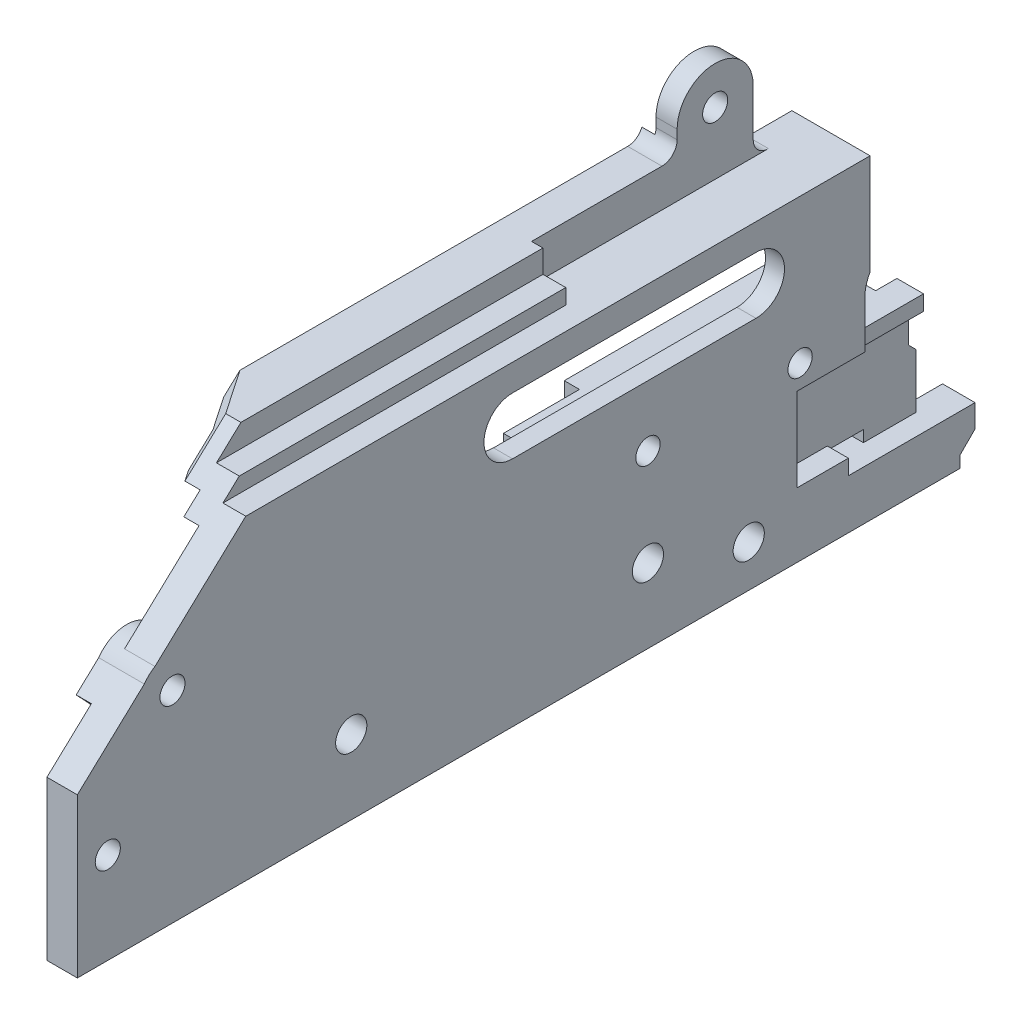
SolidWorks part; units mm, degrees
ref_plane "前视基准面" through (0, 0, 0) normal (0, 0, 1) x (1, 0, 0)
ref_plane "上视基准面" through (0, 0, 0) normal (0, 1, 0) x (1, 0, 0)
ref_plane "右视基准面" through (0, 0, 0) normal (1, 0, 0) x (0, 0, -1)
other "Configuration Table"
sketch "草图1" plane through (0, 0, 0) normal (1, 0, 0) x (0, 0, -1)
  line L0 (0, 0) -> (20, 0) construction
  line L2 (29.2, 6.5) -> (-4, 6.5)
  line L3 (29.2, 6.5) -> (29.2, -15.5)
  line L4 (29.2, -15.5) -> (-4, -15.5)
  line L5 (-4, 6.5) -> (-4, -15.5)
  circle A0 centre (0, 0) radius 1.6
  circle A1 centre (20, 0) radius 1.6
  dimension "D1" = 20
  dimension "D2" = 3.2
  dimension "D4" = 9.2
  dimension "D6" = 4
  dimension "D3" = 6.5
  dimension "D5" = 22
extrude "凸台-拉伸1" add sketch "草图1" along normal blind 7
sketch "草图2" plane through (7, 0, 0) normal (1, 0, 0) x (0, 0, -1)
  line L1 (-4, 6.5) -> (29.2, 6.5)
  line L2 (-4, 6.5) -> (-4, 17)
  line L3 (-4, 17) -> (29.2, 17)
  line L4 (29.2, 6.5) -> (29.2, 17)
  dimension "D1" = 10.5
extrude "凸台-拉伸2" add sketch "草图2" against normal offset from surface (2 mm away) 5 up to face at (0, 0, -1.6)
sketch "草图3" plane through (0, 0, 4) normal (0, 0, 1) x (1, 0, 0)
  line L1 (7, -15.5) -> (1, -15.5)
  line L2 (7, -15.5) -> (7, 6.5)
  line L3 (7, 6.5) -> (3, 6.5)
  line L4 (1, -15.5) -> (1, 4.5)
  line L5 (3, 6.5) -> (3, 4.5)
  line L6 (3, 4.5) -> (1, 4.5)
  line L7 (5, 6.5) -> (0, 6.5) construction
  dimension "D1" = 6
  dimension "D2" = 2
  dimension "D3" = 2
extrude "凸台-拉伸3" add sketch "草图3" along normal blind 60
sketch "草图4" plane through (0, 0, 4) normal (0, 0, 1) x (1, 0, 0)
  line L4 (5, 6.5) -> (7, 6.5)
  line L5 (7, 6.5) -> (7, 17)
  line L6 (7, 17) -> (5, 17)
  line L7 (5, 17) -> (5, 6.5)
  line L8 (5, 6.5) -> (7, 6.5)
  line L9 (7, 6.5) -> (7, 17)
  line L10 (7, 17) -> (5, 17)
  line L11 (5, 17) -> (5, 6.5)
  dimension "D1" = 0
extrude "凸台-拉伸4" add sketch "草图4" along normal blind 38.5
sketch "草图5" plane through (0, 0, 42.5) normal (0, 0, 1) x (1, 0, 0)
  line L0 (7, 6.5) -> (7, 17) construction
  line L1 (7, 6.5) -> (3, 6.5)
  line L2 (7, 6.5) -> (7, 17)
  line L3 (7, 17) -> (3, 17)
  line L4 (3, 6.5) -> (3, 17)
  line L5 (7, 17) -> (5, 17) construction
extrude "凸台-拉伸5" add sketch "草图5" along normal blind 2
sketch "草图6" plane through (0, 0, 44.5) normal (0, 0, 1) x (1, 0, 0)
  line L4 (7, 6.5) -> (7, 17)
  line L5 (7, 17) -> (3, 17)
  line L6 (3, 17) -> (3, 6.5)
  line L7 (3, 6.5) -> (7, 6.5)
  line L8 (7, 6.5) -> (7, 17)
  line L9 (7, 17) -> (3, 17)
  line L10 (3, 17) -> (3, 6.5)
  line L11 (3, 6.5) -> (7, 6.5)
  dimension "D1" = 0
extrude "凸台-拉伸6" add sketch "草图6" along normal up to surface (19.5 mm away) up to face at (3.6667, -1.5, 64)
sketch "草图7" plane through (0, 17, 0) normal (0, 1, 0) x (1, 0, 0)
  line L0 (1, -64) -> (1, -4) construction
  line L1 (7, 29.2) -> (1, 29.2)
  line L2 (7, 29.2) -> (7, -64)
  line L3 (7, -64) -> (1, -64)
  line L4 (1, 29.2) -> (1, -64)
  line L5 (7, -64) -> (3, -64) construction
extrude "凸台-拉伸7" add sketch "草图7" along normal blind 2
sketch "草图8" plane through (1, 0, 0) normal (-1, 0, 0) x (0, 0, 1)
  line L1 (-29.2, 19) -> (64, 19)
  line L2 (-29.2, 19) -> (-29.2, 24)
  line L3 (-29.2, 24) -> (64, 24)
  line L4 (64, 19) -> (64, 24)
  dimension "D1" = 5
extrude "凸台-拉伸8" add sketch "草图8" against normal blind 3
sketch "草图10" plane through (1, 0, 0) normal (-1, 0, 0) x (0, 0, 1)
  line L1 (-29.2, 24) -> (64, 24)
  line L2 (-29.2, 24) -> (-29.2, 22)
  line L3 (-29.2, 22) -> (64, 22)
  line L4 (64, 24) -> (64, 22)
  line L5 (64, 24) -> (64, 17) construction
  dimension "D1" = 2
extrude "凸台-拉伸9" add sketch "草图10" along normal blind 5.5
sketch "草图12" plane through (-4.5, 0, 0) normal (-1, 0, 0) x (0, 0, 1)
  line L0 (64, 24) -> (-29.2, 24) construction
  line L1 (-29.2, 22) -> (-11.2, 22)
  line L2 (-29.2, 22) -> (-29.2, 24)
  line L3 (-29.2, 24) -> (-11.2, 24)
  line L4 (-11.2, 22) -> (-11.2, 24)
  dimension "D1" = 18
extrude "切除-拉伸1" cut sketch "草图12" against normal up to surface (5.5 mm away) up to face at (1, 19.5, 17.4)
sketch "草图13" plane through (1, 0, 0) normal (-1, 0, 0) x (0, 0, 1)
  line L0 (-11.2, 22) -> (64, 22) construction
  line L1 (10.8, 22) -> (-29.2, 22)
  line L2 (10.8, 22) -> (10.8, 17)
  line L3 (10.8, 17) -> (-29.2, 17)
  line L4 (-29.2, 22) -> (-29.2, 17)
  dimension "D1" = 40
extrude "凸台-拉伸10" add sketch "草图13" along normal blind 3.5
sketch "草图14" plane through (-2.5, 0, 0) normal (-1, 0, 0) x (0, 0, 1)
  line L0 (-29.2, 17) -> (10.8, 17) construction
  line L1 (-11.2, 19.8) -> (-9.2, 19.8)
  line L2 (-11.2, 19.8) -> (-11.2, 17)
  line L3 (-11.2, 17) -> (-9.2, 17)
  line L4 (-9.2, 19.8) -> (-9.2, 17)
  line L5 (10.8, 22) -> (-11.2, 22) construction
  line L6 (-11.2, 22) -> (-11.2, 24) construction
  dimension "D1" = 2
  dimension "D2" = 2.2
sketch "草图15" plane through (4, 0, 0) normal (1, 0, 0) x (0, 0, -1)
  line L0 (29.2, 19) -> (-64, 19) construction
  line L1 (29.2, 24) -> (13.7, 24)
  line L2 (29.2, 24) -> (29.2, 19)
  line L3 (29.2, 19) -> (13.7, 19)
  line L4 (13.7, 24) -> (13.7, 19)
  line L6 (11.2, 22) -> (11.2, 24) construction
  dimension "D1" = 2.5
extrude "切除-拉伸2" cut sketch "草图15" against normal up to next
sketch "草图16" plane through (0, 22, 0) normal (0, 1, 0) x (1, 0, 0)
  line L4 (1, 11.2) -> (1, 13.7)
  line L5 (1, 13.7) -> (-2.5, 13.7)
  line L6 (-2.5, 13.7) -> (-2.5, 11.2)
  line L7 (-2.5, 11.2) -> (1, 11.2)
  line L8 (1, 11.2) -> (1, 13.7)
  line L9 (1, 13.7) -> (-2.5, 13.7)
  line L10 (-2.5, 13.7) -> (-2.5, 11.2)
  line L11 (-2.5, 11.2) -> (1, 11.2)
  dimension "D1" = 0
extrude "凸台-拉伸12" add sketch "草图16" along normal up to surface (2 mm away) up to face at (0.1667, 24, 13.0333)
sketch "草图17" plane through (7, 0, 0) normal (1, 0, 0) x (0, 0, -1)
  line L0 (-47.5, 24) -> (-64, 8.6135)
  line L1 (-64, 24) -> (13.7, 24) construction
  line L2 (-64, -15.5) -> (-64, 19) construction
  line L3 (-64, 8.6135) -> (-64, 24)
  line L4 (-64, 24) -> (-47.5, 24)
  dimension "D1" = 133
  dimension "D2" = 16.5
extrude "切除-拉伸3" cut sketch "草图17" against normal up to next
chamfer "倒角1" distance 3.5 angle 45 1 edges at (-4.5, 23, 48.5724)
sketch "草图18" plane through (-2.5, 0, 0) normal (-1, 0, 0) x (0, 0, 1)
  line L0 (-13.7, 19) -> (-13.7, 24) construction
  line L1 (-29.2, 19) -> (-13.7, 19) construction
  line L2 (-11.337, 27.2) -> (-11.337, 24)
  line L3 (-13.7, 24) -> (-11.2, 24) construction
  line L4 (-11.337, 24) -> (-13.7, 24)
  line L5 (-13.7, 24) -> (-13.7, 19)
  line L6 (-13.7, 19) -> (-21.337, 19)
  line L7 (-21.337, 19) -> (-21.337, 27.2)
  circle A0 centre (-16.337, 27.2) radius 1.65
  arc A1 (-11.337, 27.2) -> (-21.337, 27.2) centre (-16.337, 27.2) ccw
  dimension "D1" = 2.637
  dimension "D2" = 8.2
  dimension "D3" = 3.3
  dimension "D4" = 10
extrude "凸台-拉伸13" add sketch "草图18" against normal blind 2
fillet "圆角1" radius 2 2 edges at (-1.5, 24, -11.337) (-1.5, 19, -21.337)
sketch "草图19" plane through (0, 24, 0) normal (0, 1, 0) x (1, 0, 0)
  line L0 (-0.5, 9.337) -> (-0.5, 11.337) construction
  line L1 (4, 13.7) -> (-0.5, 13.7)
  line L2 (4, 13.7) -> (4, -7.8)
  line L3 (4, -7.8) -> (-0.5, -7.8)
  line L4 (-0.5, 13.7) -> (-0.5, -7.8)
  line L5 (-2.5, -10.8) -> (1, -10.8) construction
  dimension "D1" = 3
extrude "切除-拉伸4" cut sketch "草图19" against normal up to surface (5 mm away) up to face at (2, 19, -3.3438)
chamfer "倒角2" distance 3 angle 45 2 edges at (4, 24, 27.65) (1, 22, 30.2224)
sketch "草图20" plane through (7, 0, 0) normal (1, 0, 0) x (0, 0, -1)
  line L0 (-64, -15.5) -> (-64, 8.6135) construction
  line L1 (-64, -15.5) -> (29.2, -15.5) construction
  circle A0 centre (-62.5, 4) radius 1.65
  dimension "D1" = 1.5
  dimension "D2" = 19.5
  dimension "D3" = 3.3
extrude "切除-拉伸5" cut sketch "草图20" against normal up to next
sketch "草图21" plane through (1, 0, 0) normal (-1, 0, 0) x (0, 0, 1)
  circle A0 centre (62.5, 4) radius 1.65
  circle A1 centre (62.5, 4) radius 4.5
  dimension "D1" = 9
extrude "凸台-拉伸14" add sketch "草图21" against normal up to surface (6 mm away) up to face at (7, 3.3734, 35.3303)
sketch "草图22" plane through (1, 0, 0) normal (-1, 0, 0) x (0, 0, 1)
  line L3 (66.1986, 6.5633) -> (75, -1.6442)
  line L4 (75, -1.6442) -> (75, -15.5)
  line L5 (75, -15.5) -> (64, -15.5)
  line L6 (55.0066, 17) -> (64, 8.6135) construction
  line L7 (64, -0.2426) -> (64, -15.5)
  circle A2 centre (62.5, 4) radius 1.65 construction
  arc A3 (64, -0.2426) -> (58.0279, 4.5) centre (62.5, 4) ccw construction
  arc A4 (64, -0.2426) -> (66.1986, 6.5633) centre (62.5, 4) ccw
  dimension "D1" = 12.5
extrude "凸台-拉伸15" add sketch "草图22" against normal up to surface (6 mm away) up to face at (7, 3.3734, 36.2088)
sketch "草图23" plane through (7, 0, 0) normal (1, 0, 0) x (0, 0, -1)
  line L0 (-64, 8.6135) -> (-64.799, 7.8684)
  line L1 (-64.799, 7.8684) -> (-64, 8.2426)
  line L2 (-64, 8.2426) -> (-64, 8.6135)
  line L3 (-64, 8.6135) -> (-52.8618, 19) construction
  arc A0 (-64, 8.2426) -> (-66.1986, 6.5633) centre (-62.5, 4) ccw construction
extrude "凸台-拉伸16" add sketch "草图23" against normal up to surface (4 mm away) up to face at (3, 9.2872, 41.6414)
sketch "草图24" plane through (1, 0, 0) normal (-1, 0, 0) x (0, 0, 1)
  line L0 (75, -15.5) -> (75, -1.6442) construction
  line L1 (75, -15.5) -> (4, -15.5) construction
  circle A0 centre (71, -10.5) radius 1.65
  dimension "D1" = 3.3
  dimension "D2" = 4
  dimension "D3" = 5
extrude "切除-拉伸6" cut sketch "草图24" against normal up to next
sketch "草图25" plane through (5, 0, 0) normal (-1, 0, 0) x (0, 0, 1)
  line L0 (-29.2, 11.75) -> (42.5, 11.75) construction
  line L1 (-29.2, 6.5) -> (-29.2, 17) construction
  line L2 (42.5, 17) -> (42.5, 6.5) construction
  line L3 (17.8, 11.75) -> (-14.2, 11.75) construction
  line L4 (17.8, 8) -> (-14.2, 8)
  line L5 (17.8, 15.5) -> (-14.2, 15.5)
  arc A0 (17.8, 8) -> (17.8, 15.5) centre (17.8, 11.75) ccw
  arc A1 (-14.2, 15.5) -> (-14.2, 8) centre (-14.2, 11.75) ccw
  point P8 (1.8, 11.75)
  dimension "D1" = 47
  dimension "D2" = 15
  dimension "D3" = 7.5
extrude "切除-拉伸7" cut sketch "草图25" against normal up to next
sketch "草图26" plane through (0, 0, 42.5) normal (0, 0, -1) x (-1, 0, 0)
  line L4 (-5, 17) -> (-5, 6.5)
  line L5 (-5, 6.5) -> (-3, 6.5)
  line L6 (-3, 6.5) -> (-3, 17)
  line L7 (-3, 17) -> (-5, 17)
  line L8 (-5, 17) -> (-5, 6.5)
  line L9 (-5, 6.5) -> (-3, 6.5)
  line L10 (-3, 6.5) -> (-3, 17)
  line L11 (-3, 17) -> (-5, 17)
  dimension "D1" = 0
extrude "切除-拉伸8" cut sketch "草图26" against normal blind 5
sketch "草图27" plane through (0, 0, 4) normal (0, 0, 1) x (1, 0, 0)
  line L1 (1, 4.5) -> (3, 4.5)
  line L2 (1, 4.5) -> (1, 6.5)
  line L3 (1, 6.5) -> (3, 6.5)
  line L4 (3, 4.5) -> (3, 6.5)
extrude "凸台-拉伸17" add sketch "草图27" along normal blind 10
sketch "草图28" plane through (1, 0, 0) normal (-1, 0, 0) x (0, 0, 1)
  line L0 (67, 1.4943) -> (67, -15.5)
  line L2 (75, -15.5) -> (4, -15.5) construction
  line L3 (67, -15.5) -> (75, -15.5)
  line L4 (75, -15.5) -> (75, -1.6442)
  line L5 (75, -1.6442) -> (69.1556, 3.8058)
  line L6 (69.1556, 3.8058) -> (67, 1.4943)
  line L7 (75, -1.6442) -> (66.1986, 6.5633) construction
  circle A0 centre (62.5, 4) radius 1.65 construction
  dimension "D3" = 5
  dimension "D1" = 8
  dimension "D2" = 137
extrude "切除-拉伸9" cut sketch "草图28" against normal blind 2
sketch "草图29" plane through (7, 0, 0) normal (1, 0, 0) x (0, 0, -1)
  circle A0 centre (34, 3.1) radius 5.5
  circle A1 centre (20, 0) radius 1.6 construction
  dimension "D1" = 3.1
  dimension "D2" = 14
  dimension "D3" = 11
extrude "切除-拉伸10" cut sketch "草图29" against normal up to next
sketch "草图30" plane through (1, 0, 0) normal (-1, 0, 0) x (0, 0, 1)
  line L0 (4, 6.5) -> (4, -15.5) construction
  line L1 (4, -4.5) -> (67, -4.5)
  line L2 (4, -4.5) -> (4, -6.5)
  line L3 (4, -6.5) -> (67, -6.5)
  line L4 (67, -4.5) -> (67, -6.5)
  line L5 (67, 1.4943) -> (67, -15.5) construction
  circle A0 centre (0, 0) radius 1.6 construction
  dimension "D1" = 4.5
  dimension "D2" = 2
extrude "凸台-拉伸18" add sketch "草图30" along normal up to surface (1 mm away) up to face at (0, -1.9667, -18.0167)
sketch "草图31" plane through (5, 0, 0) normal (-1, 0, 0) x (0, 0, 1)
  line L0 (-14.2, 8) -> (17.8, 8) construction
  line L1 (17.8, 15.5) -> (-14.2, 15.5) construction
  line L2 (-14.2, 8) -> (17.8, 8)
  line L3 (17.8, 15.5) -> (-14.2, 15.5)
  line L4 (-29.2, 6.5) -> (47.5, 6.5)
  line L5 (47.5, 6.5) -> (47.5, 17)
  line L6 (47.5, 17) -> (-29.2, 17)
  line L7 (-29.2, 17) -> (-29.2, 6.5)
  line L8 (-29.2, 6.5) -> (47.5, 6.5)
  line L9 (47.5, 6.5) -> (47.5, 17)
  line L10 (47.5, 17) -> (-29.2, 17)
  line L11 (-29.2, 17) -> (-29.2, 6.5)
  arc A0 (17.8, 8) -> (17.8, 15.5) centre (17.8, 11.75) ccw construction
  arc A1 (-14.2, 15.5) -> (-14.2, 8) centre (-14.2, 11.75) ccw construction
  arc A2 (17.8, 8) -> (17.8, 15.5) centre (17.8, 11.75) ccw
  arc A3 (-14.2, 15.5) -> (-14.2, 8) centre (-14.2, 11.75) ccw
  dimension "D1" = 0
sketch "草图32" plane through (-2.5, 0, 0) normal (-1, 0, 0) x (0, 0, 1)
  line L8 (-11.2, 22) -> (-11.2, 25.2725)
  line L9 (-11.337, 26) -> (-11.337, 27.2)
  line L10 (-21.337, 27.2) -> (-21.337, 21)
  line L11 (-23.337, 19) -> (-29.2, 19)
  line L12 (-29.2, 19) -> (-29.2, 17)
  line L13 (-29.2, 17) -> (10.8, 17)
  line L14 (10.8, 17) -> (10.8, 22)
  line L15 (10.8, 22) -> (-11.2, 22)
  line L16 (-11.2, 22) -> (-11.2, 25.2725)
  line L17 (-11.337, 26) -> (-11.337, 27.2)
  line L18 (-21.337, 27.2) -> (-21.337, 21)
  line L19 (-23.337, 19) -> (-29.2, 19)
  line L20 (-29.2, 19) -> (-29.2, 17)
  line L21 (-29.2, 17) -> (10.8, 17)
  line L22 (10.8, 17) -> (10.8, 22)
  line L23 (10.8, 22) -> (-11.2, 22)
  circle A0 centre (-16.337, 27.2) radius 1.65 construction
  circle A1 centre (-16.337, 27.2) radius 1.65
  arc A3 (-11.337, 26) -> (-11.2, 25.2725) centre (-9.337, 26) ccw
  arc A4 (-11.337, 27.2) -> (-21.337, 27.2) centre (-16.337, 27.2) ccw
  arc A5 (-23.337, 19) -> (-21.337, 21) centre (-23.337, 21) ccw
  arc A6 (-11.337, 26) -> (-11.2, 25.2725) centre (-9.337, 26) ccw
  arc A7 (-11.337, 27.2) -> (-21.337, 27.2) centre (-16.337, 27.2) ccw
  arc A8 (-23.337, 19) -> (-21.337, 21) centre (-23.337, 21) ccw
  dimension "D1" = 0
extrude "凸台-拉伸19" add sketch "草图32" along normal blind 0.775
sketch "草图34" plane through (0, -15.5, 0) normal (0, -1, 0) x (1, 0, 0)
  line L8 (3, 75) -> (3, 67)
  line L9 (3, 67) -> (1, 67)
  line L10 (1, 67) -> (1, 4)
  line L11 (1, 4) -> (0, 4)
  line L12 (0, 4) -> (0, -29.2)
  line L13 (0, -29.2) -> (7, -29.2)
  line L14 (7, -29.2) -> (7, 75)
  line L15 (7, 75) -> (3, 75)
  line L16 (3, 75) -> (3, 67)
  line L17 (3, 67) -> (1, 67)
  line L18 (1, 67) -> (1, 4)
  line L19 (1, 4) -> (0, 4)
  line L20 (0, 4) -> (0, -29.2)
  line L21 (0, -29.2) -> (7, -29.2)
  line L22 (7, -29.2) -> (7, 75)
  line L23 (7, 75) -> (3, 75)
  dimension "D1" = 0
extrude "凸台-拉伸20" add sketch "草图34" along normal blind 5.5
sketch "草图35" plane through (0, 0, 0) normal (-1, 0, 0) x (0, 0, 1)
  line L1 (-24.2, -11) -> (-29.2, -11)
  line L2 (-24.2, -11) -> (-24.2, -21)
  line L3 (-24.2, -21) -> (-29.2, -21)
  line L4 (-29.2, -11) -> (-29.2, -21)
  dimension "D1" = 5
  dimension "D2" = 10
extrude "切除-拉伸12" cut sketch "草图35" against normal blind 1.225
sketch "草图36" plane through (0, 0, -29.2) normal (0, 0, -1) x (-1, 0, 0)
  line L1 (-1.225, -21) -> (-5.225, -21)
  line L2 (-1.225, -21) -> (-1.225, -11)
  line L3 (-1.225, -11) -> (-5.225, -11)
  line L4 (-5.225, -21) -> (-5.225, -11)
  dimension "D1" = 10
  dimension "D2" = 4
extrude "凸台-拉伸21" add sketch "草图36" along normal blind 5
sketch "草图37" plane through (5.225, 0, 0) normal (1, 0, 0) x (0, 0, -1)
  line L0 (34.2, -11) -> (34.2, -21) construction
  line L1 (33.6, -16) -> (28.85, -16)
  line L2 (33.6, -16) -> (33.6, -13)
  line L3 (33.6, -13) -> (28.85, -13)
  line L4 (28.85, -16) -> (28.85, -13)
  line L5 (34.2, -21) -> (29.2, -21) construction
  dimension "D1" = 5
  dimension "D2" = 3
  dimension "D3" = 5.35
  dimension "D4" = 0.6
extrude "切除-拉伸13" cut sketch "草图37" against normal up to next and the other way up to next
sketch "草图38" plane through (5.225, 0, 0) normal (1, 0, 0) x (0, 0, -1)
  line L0 (34.2, -11) -> (34.2, -21) construction
  line L1 (34.2, -14) -> (19.6, -14)
  line L2 (34.2, -14) -> (34.2, -3)
  line L3 (34.2, -3) -> (19.6, -3)
  line L4 (19.6, -14) -> (19.6, -3)
  line L5 (33.6, -16) -> (29.2, -16) construction
  line L7 (28.85, -16) -> (28.85, -13) construction
  dimension "D1" = 2
  dimension "D2" = 9.25
  dimension "D3" = 11
extrude "切除-拉伸14" cut sketch "草图38" along normal up to next and the other way blind 1
sketch "草图39" plane through (0, 0, -34.2) normal (0, 0, -1) x (-1, 0, 0)
  line L1 (-2.725, -1) -> (-4.225, -1)
  line L2 (-2.725, -1) -> (-2.725, -21)
  line L3 (-2.725, -21) -> (-4.225, -21)
  line L4 (-4.225, -1) -> (-4.225, -21)
  line L5 (-5.225, -21) -> (-1.225, -21) construction
  line L6 (-5.225, -14) -> (-5.225, -21) construction
  line L7 (-1.225, -11) -> (0, -11) construction
  dimension "D1" = 2.5
  dimension "D2" = 1
  dimension "D3" = 10
extrude "凸台-拉伸22" add sketch "草图39" along normal blind 5.8 and the other way up to next
sketch "草图40" plane through (0, 0, -29.2) normal (0, 0, -1) x (-1, 0, 0)
  line L1 (-1.225, -11) -> (-2.725, -11)
  line L2 (-1.225, -11) -> (-1.225, -1)
  line L3 (-1.225, -1) -> (-2.725, -1)
  line L4 (-2.725, -11) -> (-2.725, -1)
extrude "凸台-拉伸23" add sketch "草图40" along normal up to surface (5 mm away) up to face at (1.975, -16, -34.2)
sketch "草图41" plane through (4.225, 0, 0) normal (1, 0, 0) x (0, 0, -1)
  line L1 (40, -1) -> (39, -1)
  line L2 (40, -1) -> (40, -8)
  line L3 (40, -8) -> (39, -8)
  line L4 (39, -1) -> (39, -8)
  dimension "D1" = 1
  dimension "D2" = 7
extrude "切除-拉伸15" cut sketch "草图41" against normal up to next
chamfer "倒角3" distance 1 angle 45 1 edges at (3.475, -8, -39)
sketch "草图42" plane through (0, 0, -29.2) normal (0, 0, -1) x (-1, 0, 0)
  line L1 (-4.225, -21) -> (-7, -21)
  line L2 (-4.225, -21) -> (-4.225, -16)
  line L3 (-4.225, -16) -> (-7, -16)
  line L4 (-7, -21) -> (-7, -16)
extrude "凸台-拉伸24" add sketch "草图42" along normal up to surface (10.8 mm away) up to face at (3.475, -14.5, -40)
sketch "草图43" plane through (4.225, 0, 0) normal (1, 0, 0) x (0, 0, -1)
  line L4 (33.6, -16) -> (34.2, -16)
  line L5 (34.2, -16) -> (34.2, -14)
  line L6 (34.2, -14) -> (33.6, -14)
  line L7 (33.6, -14) -> (33.6, -16)
  line L8 (33.6, -16) -> (34.2, -16)
  line L9 (34.2, -16) -> (34.2, -14)
  line L10 (34.2, -14) -> (33.6, -14)
  line L11 (33.6, -14) -> (33.6, -16)
  dimension "D1" = 0
extrude "切除-拉伸16" cut sketch "草图43" along normal up to next
sketch "草图44" plane through (4.225, 0, 0) normal (1, 0, 0) x (0, 0, -1)
  line L1 (29.2, -3) -> (39, -3)
  line L2 (29.2, -3) -> (29.2, -1)
  line L3 (29.2, -1) -> (39, -1)
  line L4 (39, -3) -> (39, -1)
extrude "凸台-拉伸25" add sketch "草图44" along normal offset from surface (2 mm away) 0.775 up to face at (7, 0, -21.6)
sketch "草图45" plane through (7, 0, 0) normal (1, 0, 0) x (0, 0, -1)
  line L0 (39, -3) -> (19.6, -3) construction
  line L1 (28.5, 3.1) -> (29.3, 3.1)
  line L2 (28.5, 3.1) -> (28.5, -3)
  line L3 (28.5, -3) -> (29.3, -3)
  line L4 (29.3, 3.1) -> (29.3, -3)
  arc A0 (29.2, 5.7851) -> (29.2, 0.4149) centre (34, 3.1) ccw construction
extrude "切除-拉伸17" cut sketch "草图45" against normal up to surface (0.775 mm away) up to face at (6.225, -2, -34.1)
sketch "草图46" plane through (7, 0, 0) normal (1, 0, 0) x (0, 0, -1)
  circle A0 centre (13.25, -17) radius 2.05
  circle A1 centre (20, 0) radius 1.6 construction
  dimension "D1" = 17
  dimension "D2" = 6.75
  dimension "D3" = 4.1
extrude "切除-拉伸18" cut sketch "草图46" against normal up to next
sketch "草图47" plane through (1, 0, 0) normal (-1, 0, 0) x (0, 0, 1)
  line L0 (62.5, -0.5) -> (67, -0.5)
  line L8 (4, -4.5) -> (67, -4.5)
  line L9 (67, -4.5) -> (67, 1.4943)
  line L10 (67, 1.4943) -> (69.1556, 3.8058)
  line L11 (69.1556, 3.8058) -> (66.1986, 6.5633)
  line L12 (58.0279, 4.5) -> (14, 4.5)
  line L13 (14, 4.5) -> (14, 6.5)
  line L14 (14, 6.5) -> (4, 6.5)
  line L15 (4, 6.5) -> (4, -4.5)
  line L16 (4, -4.5) -> (67, -4.5)
  line L17 (67, -4.5) -> (67, -0.5)
  line L20 (58.0279, 4.5) -> (14, 4.5)
  line L21 (14, 4.5) -> (14, 6.5)
  line L22 (14, 6.5) -> (4, 6.5)
  line L23 (4, 6.5) -> (4, -4.5)
  arc A0 (58.0279, 4.5) -> (62.5, -0.5) centre (62.5, 4) ccw
  arc A1 (66.1986, 6.5633) -> (58.0279, 4.5) centre (62.5, 4) ccw
  dimension "D1" = 0
extrude "切除-拉伸19" cut sketch "草图47" against normal blind 1
sketch "草图48" plane through (0, -21, 0) normal (0, -1, 0) x (1, 0, 0)
  line L0 (0, 58) -> (7, 58) construction
  line L1 (3.5, 58) -> (3.5, -18) construction
  line L2 (7, -40) -> (7, 75) construction
  line L3 (7, 75) -> (3, 75) construction
  line L4 (0, 4) -> (0, 67) construction
  circle A0 centre (3.5, 58) radius 2.05
  circle A1 centre (3.5, 20) radius 2.05
  circle A2 centre (3.5, -18) radius 2.05
  dimension "D1" = 4.1
  dimension "D3" = 38
  dimension "D4" = 38
  dimension "D2" = 17
extrude "切除-拉伸20" cut sketch "草图48" against normal blind 5
sketch "草图50" plane through (0, 0, 67) normal (0, 0, 1) x (1, 0, 0)
  line L0 (0, -21) -> (0, -3.5)
  line L2 (0, -3.5) -> (0.5, -3.5)
  line L3 (0.5, -3.5) -> (0.5, -21)
  line L5 (0.5, -21) -> (0, -21)
  line L7 (0, 6.5) -> (0, -4.5) construction
  line L8 (0, -4.5) -> (2, -4.5) construction
  dimension "D1" = 0.5
  dimension "D2" = 1
extrude "切除-拉伸21" cut sketch "草图50" against normal up to next
sketch "草图51" plane through (0, 0, -28.85) normal (0, 0, -1) x (-1, 0, 0)
  line L6 (-4.225, -14) -> (-7, -14)
  line L7 (-7, -14) -> (-7, -16)
  line L8 (-7, -16) -> (-1.225, -16)
  line L9 (-1.225, -16) -> (-1.225, -13)
  line L10 (-1.225, -13) -> (-4.225, -13)
  line L11 (-4.225, -13) -> (-4.225, -14)
  line L12 (-4.225, -14) -> (-7, -14)
  line L13 (-7, -14) -> (-7, -16)
  line L14 (-7, -16) -> (-1.225, -16)
  line L15 (-1.225, -16) -> (-1.225, -13)
  line L16 (-1.225, -13) -> (-4.225, -13)
  line L17 (-4.225, -13) -> (-4.225, -14)
  dimension "D1" = 0
extrude "切除-拉伸22" cut sketch "草图51" against normal blind 3
sketch "草图52" plane through (0, -21, 0) normal (0, -1, 0) x (1, 0, 0)
  line L0 (1, 59.6583) -> (1, 56.3417)
  line L1 (1, 67) -> (1, 4) construction
  line L2 (1, 21.6583) -> (1, 18.3417)
  arc A0 (1, 59.6583) -> (1, 56.3417) centre (3.5, 58) ccw
  arc A1 (1, 21.6583) -> (1, 18.3417) centre (3.5, 20) ccw
  circle A3 centre (3.5, 20) radius 2.05 construction
  dimension "D1" = 6
extrude "凸台-拉伸26" add sketch "草图52" against normal up to surface (14.5 mm away) up to face at (0.75, -6.5, 35.5)
sketch "草图53" plane through (1, 0, 0) normal (-1, 0, 0) x (0, 0, 1)
  line L0 (67, 1.4943) -> (67, -21) construction
  line L2 (4, -21) -> (4, -19)
  line L3 (4, -19) -> (18.3417, -19)
  line L4 (67, -21) -> (67, -19)
  line L5 (21.6583, -19) -> (56.3417, -19)
  line L6 (56.3417, -6.5) -> (59.6583, -6.5)
  line L7 (56.3417, -6.5) -> (56.3417, -19)
  line L9 (59.6583, -6.5) -> (59.6583, -19)
  line L10 (18.3417, -6.5) -> (21.6583, -6.5)
  line L11 (18.3417, -6.5) -> (18.3417, -19)
  line L13 (21.6583, -6.5) -> (21.6583, -19)
  line L14 (59.6583, -19) -> (66, -19)
  line L15 (59.6583, -6.5) -> (59.6583, -21) construction
  line L16 (21.6583, -6.5) -> (21.6583, -21) construction
  line L17 (4, -21) -> (67, -21)
  line L18 (67, -6.5) -> (67, -4.5) construction
  line L19 (67, -6.5) -> (66, -6.5)
  line L20 (67, -6.5) -> (67, -19)
  line L22 (66, -6.5) -> (66, -19)
  line L23 (59.6583, -6.5) -> (67, -6.5) construction
  dimension "D1" = 2
  dimension "D2" = 1
extrude "凸台-拉伸27" add sketch "草图53" along normal up to surface (0.5 mm away) up to face at (0.5, -8.8333, 10.1)
sketch "草图54" plane through (1, 0, 0) normal (-1, 0, 0) x (0, 0, 1)
  line L0 (21.6583, -6.5) -> (56.3417, -6.5) construction
  line L1 (24.6583, -6.5) -> (53.3417, -6.5)
  line L2 (24.6583, -6.5) -> (24.6583, -19)
  line L3 (24.6583, -19) -> (53.3417, -19)
  line L4 (53.3417, -6.5) -> (53.3417, -19)
  line L5 (21.6583, -19) -> (56.3417, -19) construction
  line L6 (18.3417, -6.5) -> (18.3417, -19) construction
  line L7 (4, -6.5) -> (15.3417, -6.5)
  line L8 (4, -6.5) -> (4, -19)
  line L9 (4, -19) -> (15.3417, -19)
  line L10 (15.3417, -6.5) -> (15.3417, -19)
  line L11 (4, -19) -> (18.3417, -19) construction
  line L12 (21.6583, -6.5) -> (21.6583, -19) construction
  line L13 (56.3417, -6.5) -> (56.3417, -19) construction
  dimension "D1" = 3
  dimension "D2" = 3
  dimension "D3" = 3
extrude "切除-拉伸23" cut sketch "草图54" against normal blind 3
sketch "草图55" plane through (0.5, 0, 0) normal (-1, 0, 0) x (0, 0, 1)
  line L0 (4, -18.3367) -> (17.5807, -6.5)
  line L1 (4, -19) -> (4, -6.5) construction
  line L2 (15.3417, -6.5) -> (18.3417, -6.5) construction
  line L3 (4, -19) -> (18.3417, -6.5) construction
  line L4 (21.6583, -6.5) -> (56.3417, -19) construction
  line L5 (66, -19) -> (59.6583, -6.5) construction
  line L6 (56.3417, -6.5) -> (21.6583, -19) construction
  line L7 (18.3417, -7.1633) -> (4.761, -19)
  line L8 (18.3417, -19) -> (18.3417, -6.5) construction
  line L9 (4, -19) -> (15.3417, -19) construction
  line L10 (17.5807, -6.5) -> (18.3417, -6.5)
  line L11 (18.3417, -6.5) -> (18.3417, -7.1633)
  line L12 (4, -18.3367) -> (4, -19)
  line L13 (4, -19) -> (4.761, -19)
  line L14 (23.133, -6.5) -> (39, -12.2185)
  line L15 (21.6583, -6.5) -> (24.6583, -6.5) construction
  line L16 (56.3417, -19) -> (56.3417, -6.5) construction
  line L17 (54.867, -19) -> (39, -13.2815)
  line L18 (21.6583, -19) -> (56.3417, -19) construction
  line L19 (21.6583, -6.5) -> (21.6583, -19) construction
  line L20 (21.6583, -18.4685) -> (37.5253, -12.75)
  line L21 (21.6583, -6.5) -> (56.3417, -6.5) construction
  line L22 (23.133, -19) -> (39, -13.2815)
  line L23 (39, -12.2185) -> (54.867, -6.5)
  line L24 (40.4747, -12.75) -> (56.3417, -18.4685)
  line L25 (37.5253, -12.75) -> (21.6583, -7.0315)
  line L26 (40.4747, -12.75) -> (56.3417, -7.0315)
  line L27 (23.133, -6.5) -> (21.6583, -6.5)
  line L28 (21.6583, -6.5) -> (21.6583, -7.0315)
  line L29 (54.867, -6.5) -> (56.3417, -6.5)
  line L30 (56.3417, -6.5) -> (56.3417, -7.0315)
  line L31 (56.3417, -18.4685) -> (56.3417, -19)
  line L32 (56.3417, -19) -> (54.867, -19)
  line L33 (23.133, -19) -> (21.6583, -19)
  line L34 (21.6583, -19) -> (21.6583, -18.4685)
  line L35 (59.6583, -7.6051) -> (65.4393, -19)
  line L36 (59.6583, -6.5) -> (59.6583, -19) construction
  line L37 (59.6583, -19) -> (66, -19) construction
  line L38 (60.219, -6.5) -> (66, -17.8949)
  line L39 (59.6583, -6.5) -> (66, -6.5) construction
  line L40 (66, -6.5) -> (66, -19) construction
  line L41 (59.6583, -7.6051) -> (59.6583, -6.5)
  line L42 (59.6583, -6.5) -> (60.219, -6.5)
  line L43 (66, -17.8949) -> (66, -19)
  line L44 (66, -19) -> (65.4393, -19)
  dimension "D1" = 1
  dimension "D2" = 1
  dimension "D3" = 1
  dimension "D4" = 1
extrude "凸台-拉伸28" add sketch "草图55" against normal up to next
fillet "圆角2" radius 0.8 30 edges at (0.75, -19, 18.3417) (2.5, -19, 15.3417) (2.5, -6.5, 15.3417) (2.25, -6.5, 4) (0.75, -7.1633, 18.3417) (0.75, -6.5, 17.5807) (2.5, -9.778, 15.3417) (2.5, -8.4515, 15.3417) (2.25, -18.3367, 4) (2.25, -19, 4.761) (2.25, -12.75, 37.5253) (2.25, -13.2815, 39) (2.25, -12.2185, 39) (2.25, -12.75, 40.4747) (2.5, -8.1127, 53.3417) (2.5, -17.3873, 53.3417) (0.75, -18.4685, 56.3417) (0.75, -7.0315, 56.3417) (0.75, -6.5, 54.867) (0.75, -19, 54.867) (0.75, -19, 23.133) (0.75, -6.5, 23.133) (0.75, -18.4685, 21.6583) (0.75, -7.0315, 21.6583) (0.75, -17.8949, 66) (0.75, -19, 59.6583) (0.75, -19, 65.4393) (0.75, -6.5, 66) (0.75, -6.5, 60.219) (0.75, -7.6051, 59.6583)
sketch "草图56" plane through (0.5, 0, 0) normal (-1, 0, 0) x (0, 0, 1)
  line L0 (35.9658, -12.75) -> (42.0342, -12.75) construction
  line L1 (39, -12.1681) -> (39, -13.3319) construction
  arc A0 (35.4371, -13.5026) -> (35.4371, -11.9974) centre (35.1658, -12.75) ccw construction
  arc A1 (42.5629, -11.9974) -> (42.5629, -13.5026) centre (42.8342, -12.75) ccw construction
  arc A2 (38.7288, -12.1208) -> (39.2712, -12.1208) centre (39, -11.3681) ccw construction
  arc A3 (39.2712, -13.3792) -> (38.7288, -13.3792) centre (39, -14.1319) ccw construction
  circle A4 centre (39, -12.75) radius 2.05
  circle A5 centre (39, -12.75) radius 4
  dimension "D1" = 4.1
  dimension "D2" = 8
extrude "凸台-拉伸29" add sketch "草图56" against normal up to next (3.5 mm away)
fillet "圆角3" radius 0.8 8 edges at (2.25, -14.566, 35.436) (2.25, -14.566, 42.564) (2.25, -13.6252, 42.9031) (2.25, -11.8748, 42.9031) (2.25, -10.934, 42.564) (2.25, -10.934, 35.436) (2.25, -13.6252, 35.0969) (2.25, -11.8748, 35.0969)
sketch "草图57" plane through (0.5, 0, 0) normal (-1, 0, 0) x (0, 0, 1)
  line L0 (0, 0) -> (0, -12.75) construction
  line L1 (0, -12.75) -> (39, -12.75) construction
  circle A0 centre (39, -12.75) radius 2.05
  circle A1 centre (0, -12.75) radius 2.05
extrude "切除-拉伸24" cut sketch "草图57" against normal up to next
sketch "草图58" plane through (0.5, 0, 0) normal (-1, 0, 0) x (0, 0, 1)
  line L0 (-29.2, -3.5) -> (4, -3.5) construction
  line L1 (-19.2, -4.5) -> (-4, -4.5)
  line L2 (-19.2, -4.5) -> (-19.2, -13)
  line L3 (-19.2, -13) -> (-4, -13)
  line L4 (-4, -4.5) -> (-4, -13)
  line L5 (-24.2, -11) -> (-24.2, -21) construction
  circle A0 centre (-13.25, -17) radius 2.05 construction
  circle A1 centre (0, -12.75) radius 2.05 construction
  dimension "D1" = 4
  dimension "D2" = 4
  dimension "D3" = 1
  dimension "D4" = 5
extrude "切除-拉伸25" cut sketch "草图58" against normal up to surface (3.5 mm away) up to face at (4, -9.7828, 9.7862)
fillet "圆角4" radius 0.8 4 edges at (2.25, -13, -4) (2.25, -13, -19.2) (2.25, -4.5, -19.2) (2.25, -4.5, -4)
extrude "凸台-拉伸30" add sketch "草图31" along normal blind 0.5
sketch "草图59" plane through (2.725, 0, 0) normal (-1, 0, 0) x (0, 0, 1)
  line L0 (-25.85, -13) -> (-33.6, -13) construction
  line L1 (-34.2, -21) -> (-31.6, -21)
  line L2 (-34.2, -21) -> (-34.2, -11)
  line L3 (-34.2, -11) -> (-31.6, -11)
  line L4 (-31.6, -21) -> (-31.6, -11)
  line L5 (-33.6, -13) -> (-33.6, -16) construction
  dimension "D1" = 2
  dimension "D2" = 2
extrude "切除-拉伸26" cut sketch "草图59" along normal up to next
sketch "草图60" plane through (2.725, 0, 0) normal (-1, 0, 0) x (0, 0, 1)
  line L0 (-37, -1) -> (-37, -7.8284)
  line L1 (-34.2, -1) -> (-39, -1) construction
  line L2 (-37, -7.8284) -> (-38, -8.8284)
  line L4 (-38, -8.8284) -> (-38, -21)
  line L5 (-40, -21) -> (-31.6, -21) construction
  line L6 (-38, -21) -> (-40, -21)
  line L7 (-40, -21) -> (-40, -8)
  line L8 (-40, -8) -> (-39, -7)
  line L9 (-39, -7) -> (-39, -1)
  line L10 (-39, -1) -> (-37, -1)
  dimension "D1" = 2
  dimension "D2" = 2
  dimension "D3" = 2
extrude "切除-拉伸27" cut sketch "草图60" against normal up to next
sketch "草图61" plane through (4.225, 0, 0) normal (1, 0, 0) x (0, 0, -1)
  line L0 (32.6, -16) -> (32.6, -14.5)
  line L1 (38, -16) -> (25.85, -16) construction
  line L2 (32.6, -14.5) -> (27.35, -14.5)
  line L3 (27.35, -14.5) -> (27.35, -16)
  line L4 (27.35, -16) -> (25.85, -16)
  line L5 (25.85, -16) -> (25.85, -13)
  line L6 (25.85, -13) -> (33.6, -13)
  line L7 (33.6, -13) -> (33.6, -16)
  line L8 (33.6, -16) -> (32.6, -16)
  dimension "D1" = 1.5
  dimension "D2" = 1
  dimension "D3" = 1.5
extrude "凸台-拉伸31" add sketch "草图61" against normal up to surface (1.5 mm away) up to face at (2.725, -11.7214, -34.3333)
sketch "草图62" plane through (0, 0, -25.85) normal (0, 0, -1) x (-1, 0, 0)
  line L4 (-4.225, -16) -> (-4.225, -14)
  line L5 (-4.225, -14) -> (-7, -14)
  line L6 (-7, -14) -> (-7, -16)
  line L7 (-7, -16) -> (-4.225, -16)
  line L8 (-4.225, -16) -> (-4.225, -14)
  line L9 (-4.225, -14) -> (-7, -14)
  line L10 (-7, -14) -> (-7, -16)
  line L11 (-7, -16) -> (-4.225, -16)
  dimension "D1" = 0
extrude "凸台-拉伸32" add sketch "草图62" along normal up to surface (1.5 mm away) up to face at (3.475, -15.25, -27.35)
sketch "草图63" plane through (2.725, 0, 0) normal (-1, 0, 0) x (0, 0, 1)
  line L0 (-31.6, -13) -> (-31.6, -14.5)
  line L1 (-27.35, -14.5) -> (-32.6, -14.5) construction
  line L2 (-31.6, -14.5) -> (-27.35, -14.5)
  line L3 (-27.35, -14.5) -> (-27.35, -16)
  line L4 (-27.35, -16) -> (-25.85, -16)
  line L5 (-25.85, -16) -> (-25.85, -13)
  line L6 (-25.85, -13) -> (-31.6, -13)
extrude "凸台-拉伸33" add sketch "草图63" along normal up to surface (1.5 mm away) up to face at (1.225, -12.1667, -29.4417)
sketch "草图64" plane through (0, 0, -38) normal (0, 0, -1) x (-1, 0, 0)
  line L1 (-7, -16) -> (-2.725, -16)
  line L2 (-7, -16) -> (-7, -21)
  line L3 (-7, -21) -> (-2.725, -21)
  line L4 (-2.725, -16) -> (-2.725, -21)
extrude "凸台-拉伸34" add sketch "草图64" along normal blind 5
chamfer "倒角4" distance 2 angle 45 1 edges at (4.8625, -21, -43)
sketch "草图65" plane through (0, -21, 0) normal (0, -1, 0) x (1, 0, 0)
  line L10 (2.725, -31.6) -> (2.725, -41)
  line L11 (2.725, -41) -> (7, -41)
  line L12 (7, -41) -> (7, 75)
  line L13 (7, 75) -> (3, 75)
  line L14 (3, 75) -> (3, 67)
  line L15 (3, 67) -> (0.5, 67)
  line L16 (0.5, 67) -> (0.5, -24.2)
  line L17 (0.5, -24.2) -> (1.225, -24.2)
  line L18 (1.225, -24.2) -> (1.225, -31.6)
  line L19 (1.225, -31.6) -> (2.725, -31.6)
  line L20 (2.725, -31.6) -> (2.725, -41)
  line L21 (2.725, -41) -> (7, -41)
  line L22 (7, -41) -> (7, 75)
  line L23 (7, 75) -> (3, 75)
  line L24 (3, 75) -> (3, 67)
  line L25 (3, 67) -> (0.5, 67)
  line L26 (0.5, 67) -> (0.5, -24.2)
  line L27 (0.5, -24.2) -> (1.225, -24.2)
  line L28 (1.225, -24.2) -> (1.225, -31.6)
  line L29 (1.225, -31.6) -> (2.725, -31.6)
  circle A0 centre (3.5, -18) radius 2.05 construction
  circle A1 centre (3.5, 20) radius 2.05 construction
  circle A2 centre (3.5, 58) radius 2.05 construction
  circle A3 centre (3.5, -18) radius 2.05
  circle A4 centre (3.5, 20) radius 2.05
  circle A5 centre (3.5, 58) radius 2.05
  dimension "D1" = 0
extrude "凸台-拉伸35" add sketch "草图65" along normal blind 1.5
sketch "草图66" plane through (0, 0, -27.35) normal (0, 0, -1) x (-1, 0, 0)
  line L6 (-7, -16) -> (-1.225, -16)
  line L7 (-1.225, -16) -> (-1.225, -14.5)
  line L8 (-1.225, -14.5) -> (-4.225, -14.5)
  line L9 (-4.225, -14.5) -> (-4.225, -14)
  line L10 (-4.225, -14) -> (-7, -14)
  line L11 (-7, -14) -> (-7, -16)
  line L12 (-7, -16) -> (-1.225, -16)
  line L13 (-1.225, -16) -> (-1.225, -14.5)
  line L14 (-1.225, -14.5) -> (-4.225, -14.5)
  line L15 (-4.225, -14.5) -> (-4.225, -14)
  line L16 (-4.225, -14) -> (-7, -14)
  line L17 (-7, -14) -> (-7, -16)
  dimension "D1" = 0
extrude "切除-拉伸28" cut sketch "草图66" against normal blind 1
sketch "草图67" plane through (0, 0, -32.6) normal (0, 0, 1) x (1, 0, 0)
  line L4 (4.225, -14.5) -> (2.725, -14.5)
  line L5 (2.725, -14.5) -> (2.725, -16)
  line L6 (2.725, -16) -> (4.225, -16)
  line L7 (4.225, -16) -> (4.225, -14.5)
  line L8 (4.225, -14.5) -> (2.725, -14.5)
  line L9 (2.725, -14.5) -> (2.725, -16)
  line L10 (2.725, -16) -> (4.225, -16)
  line L11 (4.225, -16) -> (4.225, -14.5)
  dimension "D1" = 0
extrude "凸台-拉伸36" add sketch "草图67" along normal blind 1.5
sketch "草图68" plane through (0, 0, 7.8) normal (0, 0, -1) x (-1, 0, 0)
  line L0 (-1, 24) -> (-4, 21)
  line L1 (-4, 21) -> (-1, 21)
  line L2 (-1, 21) -> (-1, 24)
extrude "切除-拉伸29" cut sketch "草图68" against normal up to next
sketch "草图69" plane through (0, 0, 10.8) normal (0, 0, 1) x (1, 0, 0)
  line L0 (-2, 22) -> (1, 19)
  line L1 (1, 19) -> (-2, 19)
  line L2 (-2, 19) -> (-2, 22)
extrude "凸台-拉伸37" add sketch "草图69" along normal up to surface (42.0618 mm away) up to face at (2.5, 18.1447, 53.779)
sketch "草图70" plane through (0, 24, 0) normal (0, 1, 0) x (1, 0, 0)
  line L0 (-4.5, -42.368) -> (-4.5, -52.8618)
  line L1 (-4.5, -52.8618) -> (-1, -52.8618)
  line L2 (1, -52.8618) -> (-2, -52.8618) construction
  line L3 (-1, -52.8618) -> (-1, -47.5)
  line L4 (-1, -47.5) -> (-4.5, -42.368)
extrude "切除-拉伸30" cut sketch "草图70" along direction (0, -0.682, 0.7314) on the side against the normal blind 10
sketch "草图71" plane through (-4.5, 0, 0) normal (-1, 0, 0) x (0, 0, 1)
  line L4 (-11.2, 22) -> (44.5128, 22)
  line L5 (44.5128, 22) -> (42.368, 24)
  line L6 (42.368, 24) -> (-9.337, 24)
  line L7 (-11.2, 25.2725) -> (-11.2, 22)
  line L8 (-11.2, 22) -> (44.5128, 22)
  line L9 (44.5128, 22) -> (42.368, 24)
  line L10 (42.368, 24) -> (-9.337, 24)
  line L11 (-11.2, 25.2725) -> (-11.2, 22)
  arc A1 (-11.2, 25.2725) -> (-9.337, 24) centre (-9.337, 26) ccw
  arc A2 (-11.2, 25.2725) -> (-9.337, 24) centre (-9.337, 26) ccw
  dimension "D1" = 0
extrude "凸台-拉伸38" add sketch "草图71" along normal blind 0.5
sketch "草图72" plane through (0, 24, 0) normal (0, 1, 0) x (1, 0, 0)
  line L0 (-4.5, -42.368) -> (-5, -41.6349)
  line L1 (-5, -42.368) -> (-5, 9.337) construction
  line L2 (-5, -41.6349) -> (-5, -42.368)
  line L3 (-5, -42.368) -> (-4.5, -42.368)
  line L4 (-4.5, -42.368) -> (-1, -47.5) construction
extrude "切除-拉伸31" cut sketch "草图72" along direction (0, 0.682, -0.7314) on the side against the normal up to next (2 mm away)
